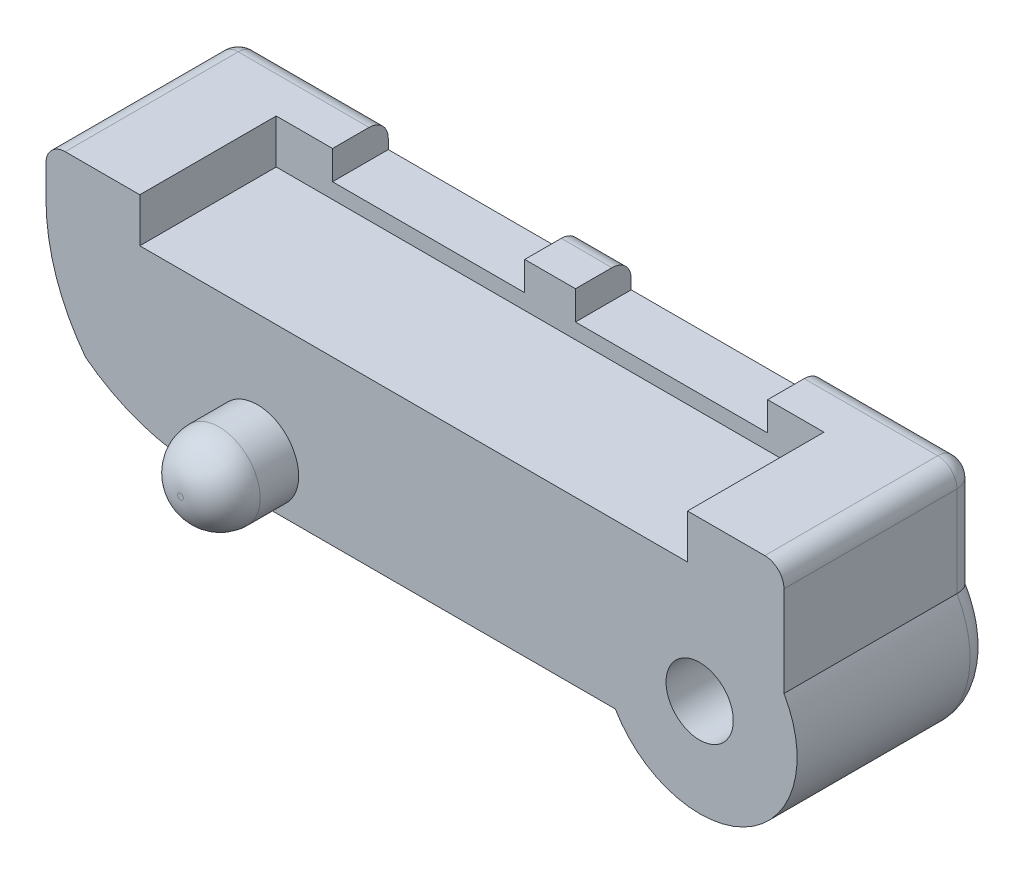
SolidWorks part; units mm, degrees
ref_plane "Alzado" through (0, 0, 0) normal (0, 0, 1) x (1, 0, 0)
ref_plane "Planta" through (0, 0, 0) normal (0, 1, 0) x (1, 0, 0)
ref_plane "Vista lateral" through (0, 0, 0) normal (1, 0, 0) x (0, 0, -1)
sketch "Croquis1" plane through (0, 0, 0) normal (0, 1, 0) x (1, 0, 0)
  line L1 (-16.5, 2.5) -> (16.5, 2.5)
  line L2 (-16.5, 2.5) -> (-16.5, -2.5)
  line L3 (-16.5, -2.5) -> (16.5, -2.5)
  line L4 (16.5, 2.5) -> (16.5, -2.5)
  line L5 (-16.5, 2.5) -> (16.5, -2.5) construction
  line L6 (-16.5, -2.5) -> (16.5, 2.5) construction
  point P0 (0, 0)
  dimension "D1" = 33
  dimension "D2" = 5
extrude "Saliente-Extruir1" add sketch "Croquis1" along normal blind 8.5
sketch "Croquis2" plane through (16.5, 0, 0) normal (1, 0, 0) x (0, 0, -1)
  line L4 (-2.5, 0) -> (2.5, 0)
  line L5 (2.5, 0) -> (2.5, 8.5)
  line L6 (2.5, 8.5) -> (-2.5, 8.5)
  line L7 (-2.5, 8.5) -> (-2.5, 0)
  line L8 (-2.5, 0) -> (2.5, 0)
  line L9 (2.5, 0) -> (2.5, 8.5)
  line L10 (2.5, 8.5) -> (-2.5, 8.5)
  line L11 (-2.5, 8.5) -> (-2.5, 0)
  dimension "D1" = 0
extrude "Saliente-Extruir2" add sketch "Croquis2" along normal blind 14
sketch "Croquis4" plane through (0, 0, -2.5) normal (0, 0, -1) x (-1, 0, 0)
  line L0 (-21.8988, 8.5) -> (-21.8988, 2.7534)
  line L1 (-21.8988, 2.7534) -> (-21.8988, 0)
  line L4 (-30.5, 0) -> (16.5, 0)
  line L5 (16.5, 0) -> (16.5, 8.5)
  line L6 (16.5, 8.5) -> (-30.5, 8.5)
  line L7 (-30.5, 8.5) -> (-30.5, 0)
  line L8 (-30.5, 0) -> (-21.8988, 0)
  line L10 (-21.8988, 8.5) -> (-30.5, 8.5)
  line L11 (-30.5, 8.5) -> (-30.5, 0)
  dimension "D1" = 0
extrude "Cortar-Extruir1" cut sketch "Croquis4" against normal up to surface (5 mm away)
sketch "Croquis5" plane through (0, 0, -2.5) normal (0, 0, -1) x (-1, 0, 0)
  circle A0 centre (-17.5113, 2.542) radius 5.0707
extrude "Saliente-Extruir3" add sketch "Croquis5" against normal up to surface (5 mm away) up to face at (2.6994, 4.25, 2.5)
sketch "Croquis6" plane through (0, 0, -2.5) normal (0, 0, -1) x (-1, 0, 0)
  circle A0 centre (-17.5113, 2.542) radius 1.75
  dimension "D1" = 3.5
extrude "Cortar-Extruir2" cut sketch "Croquis6" against normal up to surface (5 mm away) up to face at (5.2927, 3.5393, 2.5)
sketch "Croquis7" plane through (0, 0, -2.5) normal (0, 0, -1) x (-1, 0, 0)
  line L4 (-21.8988, 8.5) -> (-21.8988, 5.0839)
  line L5 (-13.1238, 0) -> (16.5, 0)
  line L6 (16.5, 0) -> (16.5, 8.5)
  line L7 (16.5, 8.5) -> (-21.8988, 8.5)
  line L8 (-21.8988, 8.5) -> (-21.8988, 5.0839)
  line L9 (-13.1238, 0) -> (16.5, 0)
  line L10 (16.5, 0) -> (16.5, 8.5)
  line L11 (16.5, 8.5) -> (-21.8988, 8.5)
  circle A0 centre (-17.5113, 2.542) radius 3.5
  arc A1 (-21.8988, 5.0839) -> (-13.1238, 0) centre (-17.5113, 2.542) ccw
  arc A2 (-21.8988, 5.0839) -> (-13.1238, 0) centre (-17.5113, 2.542) ccw
  dimension "D2" = 7
  dimension "D1" = 0
extrude "Saliente-Extruir4" add sketch "Croquis7" along normal blind 5 contours L8 A2 L9 L10 L11 | A0
sketch "Croquis8" plane through (0, 8.5, 0) normal (0, 1, 0) x (1, 0, 0)
  line L4 (-16.5, -2.5) -> (21.8988, -2.5)
  line L5 (21.8988, -2.5) -> (21.8988, 7.5)
  line L6 (21.8988, 7.5) -> (-16.5, 7.5)
  line L7 (-16.5, 7.5) -> (-16.5, -2.5)
  line L8 (-16.5, -2.5) -> (-11.6205, -2.5)
  line L9 (21.8988, -2.5) -> (21.8988, 7.5)
  line L10 (21.8988, 7.5) -> (-16.5, 7.5)
  line L11 (-16.5, 7.5) -> (-16.5, -2.5)
  line L13 (16.8795, -2.5) -> (21.8988, -2.5)
  line L14 (16.8795, 4.6) -> (-11.6205, 4.6)
  line L15 (-11.6205, 4.6) -> (-11.6205, -2.1)
  line L21 (16.8795, 4.6) -> (16.8795, -2.1)
  line L22 (16.8795, -2.1) -> (16.8795, -2.5)
  line L23 (-11.6205, -2.1) -> (-11.6205, -2.5)
  line L24 (-16.5, -2.5) -> (-11.2205, -2.5) construction
  line L25 (16.4795, 4.2) -> (-11.2205, 4.2) construction
  line L26 (-11.2205, 4.2) -> (-11.2205, -2.5) construction
  line L27 (-16.1, -2.1) -> (-11.6205, -2.1) construction
  line L28 (21.4988, 7.1) -> (-16.1, 7.1) construction
  line L29 (-16.1, 7.1) -> (-16.1, -2.1) construction
  line L30 (21.4988, -2.1) -> (21.4988, 7.1) construction
  line L31 (16.8795, -2.1) -> (21.4988, -2.1) construction
  line L32 (16.4795, 4.2) -> (16.4795, -2.5) construction
  line L33 (16.4795, -2.5) -> (21.8988, -2.5) construction
  dimension "D1" = 0
  dimension "D2" = 0.4
extrude "Saliente-Extruir5" add sketch "Croquis8" along normal up to vertex (1.6 mm away)
sketch "Croquis9" plane through (0, 10.8, 0) normal (0, 1, 0) x (1, 0, 0)
  line L0 (-11.6205, 4.6) -> (16.8795, 4.6) construction
  line L1 (13.9495, 4.6) -> (3.9495, 4.6)
  line L2 (13.9495, 4.6) -> (13.9495, 7.5)
  line L3 (13.9495, 7.5) -> (3.9495, 7.5)
  line L4 (3.9495, 4.6) -> (3.9495, 7.5)
  line L5 (21.8988, 7.5) -> (-16.5, 7.5) construction
  line L7 (1.3095, 4.6) -> (-8.6905, 4.6)
  line L8 (1.3095, 4.6) -> (1.3095, 7.5)
  line L9 (1.3095, 7.5) -> (-8.6905, 7.5)
  line L10 (-8.6905, 4.6) -> (-8.6905, 7.5)
extrude "Cortar-Extruir3" cut sketch "Croquis9" against normal blind 1.5
chamfer "Chaflán1" distance 4 angle 45 1 edges at (-16.5, 0, -2.5)
fillet "Redondeo1" radius 10 2 edges at (-12.5, 0, -2.5) (-16.5, 4, -2.5)
fillet "Redondeo3" radius 1 4 edges at (-15.9707, 4.9318, -7.5) (-11.5682, 0.5293, -7.5) (2.383, 0, -7.5) (-16.5, 9.4711, -7.5)
fillet "Redondeo4" radius 1 2 edges at (19.5653, -2.0941, -7.5) (21.8988, 7.942, -7.5)
fillet "Redondeo5" radius 1 3 edges at (21.8988, 10.8, -2) (21.6059, 10.8, -7.2071) (17.4242, 10.8, -7.5)
fillet "Redondeo6" radius 1 3 edges at (-12.0953, 10.8, -7.5) (-16.2071, 10.8, -7.2071) (-16.5, 10.8, -2)
fillet "Redondeo7" radius 1 1 edges at (2.6295, 10.8, -7.5)
sketch "Croquis10" plane through (0, 0, 2.5) normal (0, 0, 1) x (1, 0, 0)
  circle A0 centre (-5.5033, 2.2525) radius 2.15
  dimension "D1" = 4.3
extrude "Saliente-Extruir6" add sketch "Croquis10" along normal blind 4
fillet "Redondeo8" radius 2 1 edges at (-3.3533, 2.2525, 6.5)
